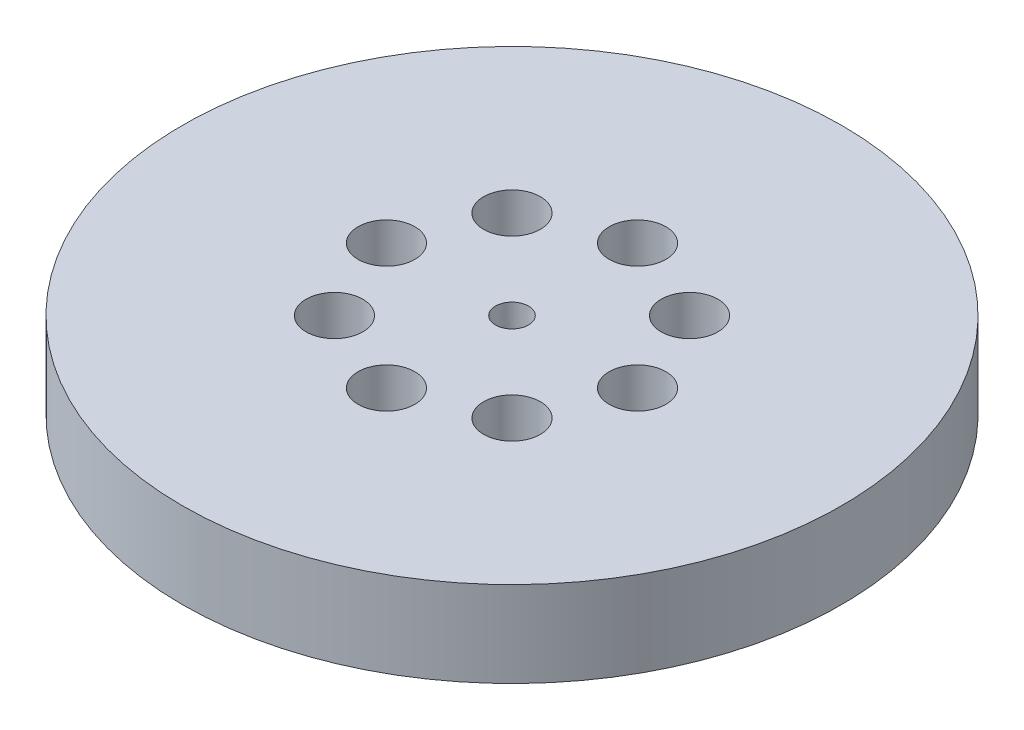
SolidWorks part; units mm, degrees
ref_plane "Front Plane" through (0, 0, 0) normal (0, 0, 1) x (1, 0, 0)
ref_plane "Top Plane" through (0, 0, 0) normal (0, 1, 0) x (1, 0, 0)
ref_plane "Right Plane" through (0, 0, 0) normal (1, 0, 0) x (0, 0, -1)
sketch "Sketch1" plane through (0, 0, 0) normal (0, 1, 0) x (1, 0, 0)
  circle A0 centre (0, 0) radius 100
  dimension "FLANGE_OD" = 200
extrude "Boss-Extrude1" add sketch "Sketch1" along normal blind 26
sketch "Sketch2" plane through (0, 0, 0) normal (0, 1, 0) x (1, 0, 0)
  circle A0 centre (0, 0) radius 5
  dimension "BORE_D" = 10
extrude "Cut-Extrude1" cut sketch "Sketch2" along normal through all
sketch "Sketch3" plane through (0, 26, 0) normal (0, 1, 0) x (1, 0, 0)
  circle A0 centre (0, 0) radius 38.0948 construction
  circle A1 centre (-38.0948, 0) radius 8.6057
  dimension "BOLT_D" = 17.2115
  dimension "BOLT_PCD" = 76.1896
extrude "Cut-Extrude2" cut sketch "Sketch3" against normal blind 20.9498
pattern_circular "CirPattern1" count 8 over 360 about axis through (0, 0, 0) along (0, 1, 0) of "Cut-Extrude2"
